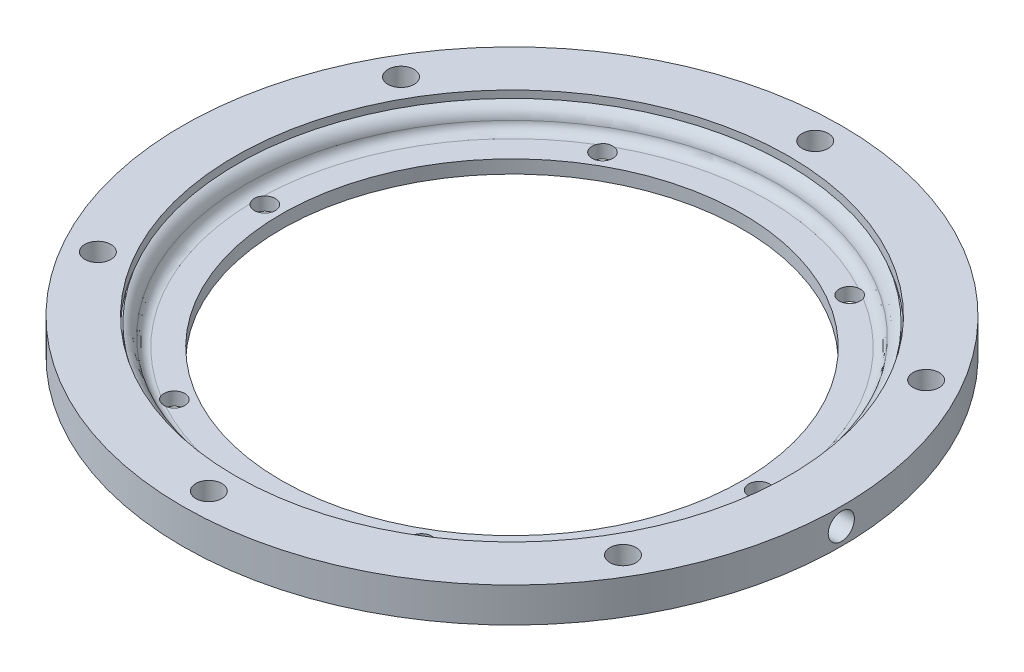
SolidWorks part; units mm, degrees
note: '?' marks a value the reader was unsure of.
ref_plane "Front" through (0, 0, 0) normal (0, 0, 1) x (1, 0, 0)
ref_plane "Top" through (0, 0, 0) normal (0, 1, 0) x (1, 0, 0)
ref_plane "Right" through (0, 0, 0) normal (1, 0, 0) x (0, 0, -1)
ref_axis "Axis1" through (0, 12.8283, 0) along (0, -1, 0)?
sketch "Sketch1" plane through (0, 0, 0) normal (0, 0, 1) x (1, 0, 0)
  line L0 (0, 8.551) -> (0, -4.9357) construction
  line L1 (100, 12.2174) -> (100, 1.6954)
  line L2 (100, 12.2174) -> (84, 12.2174)
  line L3 (84, 12.2174) -> (84, 9.0402)
  line L4 (87, 1.6954) -> (100, 1.6954)
  line L5 (70.016, 0) -> (85.5, 0)
  line L6 (70.016, 0) -> (100, 12.2174) construction
  line L7 (87, 1.6954) -> (87, 3.7334)
  line L9 (70.016, 4) -> (70.016, 0)
  line L10 (84, 9.0402) -> (87, 3.7334) construction
  line L11 (85.5, 0) -> (85.5, 3.048)
  line L12 (83.5, 10.3485) -> (83.5, 8.8172)
  line L13 (77.5, 4) -> (70.016, 4)
  arc A0 (83.5, 8.8172) -> (85.5, 3.048) centre (85.008, 6.1087) ccw
  arc A1 (83.5, 10.3485) -> (80.5444, 6.6797) centre (85.008, 6.1087) ccw
  arc A2 (77.5, 4) -> (80.5444, 6.6797) centre (77.5, 7.0692) ccw
  arc A3 (87, 3.7334) -> (84, 9.0402) centre (85.008, 6.1087) ccw
  point P17 (85.5, 6.3868)
  dimension "D8" = 6.2
  dimension "D9" = 9
  dimension "D2" = 12.2174
  dimension "D3" = 29.984
  dimension "D4" = 16
  dimension "D5" = 10.522
  dimension "D6" = 13
  dimension "D7" = 4
  dimension "D10" = 0.5
  dimension "D11" = 200
  dimension "D12" = 155
  dimension "D13" = 1.6954
  dimension "D14" = 140.032
revolve "Revolve2" add sketch "Sketch1" angle 360 about L0
sketch "Sketch2" plane through (0, 0, 0) normal (0, -1, 0) x (1, 0, 0)
  line L0 (0, 0) -> (167.0886, 0) construction
  line L1 (0, 0) -> (86.0025, -148.9607) construction
  line L2 (70.016, 4.1036) -> (70.016, -4.7686) construction
  line L3 (72.016, 3.5121) -> (72.016, -5.9515) construction
  line L4 (77.5, 0) -> (82.984, 0) construction
  line L5 (72.016, 0) -> (77.5, 0) construction
  line L6 (139.657, -6.35) -> (135.2215, -6.35) construction
  line L7 (73.5238, -114.647) -> (75.5358, -118.1318) construction
  arc A0 (45.1091, -56.138) -> (71.1715, -10.9966) centre (0, 0) ccw
  arc A1 (51.9792, -64.6878) -> (82.0109, -12.6714) centre (0, 0) ccw
  circle A2 centre (0, 0) radius 77.5 construction
  circle A3 centre (0, 0) radius 70.016 construction
  arc A4 (82.0109, -12.6714) -> (71.1715, -10.9966) centre (76.5912, -11.834) ccw
  arc A5 (45.1091, -56.138) -> (51.9792, -64.6878) centre (48.5441, -60.4129) ccw
  dimension "D2" = 155
  dimension "D1" = 60
  dimension "D3" = 2
  dimension "D4" = 6.35
  dimension "D5" = 6.35
extrude "Cut-Extrude1" cut sketch "Sketch2" against normal offset from surface (2.916 mm away) 3.81
pattern_circular "CirPattern1" count 6 over 360 about axis through (0, 0, 0) along (0, 1, 0) of "Cut-Extrude1"
sketch "Sketch3" plane through (0, 1.6954, 0) normal (0, -1, 0) x (1, 0, 0)
  line L0 (0, 0) -> (87, 50.2295) construction
  line L1 (0, 0) -> (154.2972, -89.0835) construction
  line L2 (0, 0) -> (63.0511, 0) construction
  line L3 (88.5604, 41.9649) -> (80.7379, 37.4486)
  line L4 (80.7379, -37.4486) -> (88.5604, -41.9649)
  line L5 (100, 4.9183) -> (100, -33.5059) construction
  line L6 (98, 8.5668) -> (98, -35.0892) construction
  line L7 (89, 7.4564) -> (89, -22.8744) construction
  line L8 (87, -1.1233) -> (87, -18.1031) construction
  arc A0 (88.5604, -41.9649) -> (88.5604, 41.9649) centre (0, 0) ccw
  arc A1 (80.7379, -37.4486) -> (80.7379, 37.4486) centre (0, 0) ccw
  circle A2 centre (0, 0) radius 87 construction
  circle A3 centre (0, 0) radius 100 construction
  dimension "D1" = 60
  dimension "D2" = 30
  dimension "D3" = 7.9375
  dimension "D4" = 7.9375
  dimension "D5" = 2
  dimension "D6" = 2
extrude "Cut-Extrude2" cut sketch "Sketch3" against normal blind 10
pattern_circular "CirPattern2" count 6 over 360 about axis through (0, 0, 0) along (0, 1, 0) of "Cut-Extrude2"
sketch "Sketch5" plane through (0, 4, 0) normal (0, 1, 0) x (-1, 0, 0)
  line L0 (0, 0) -> (-37.5, -64.9519) construction
  line L1 (17.7406, -10.2426) -> (-18.7249, 10.8108) construction
  line L2 (0, 0) -> (0, -87.4239) construction
  circle A0 centre (-37.5, -64.9519) radius 3.175
  dimension "D1" = 6.35
  dimension "D2" = 150
  dimension "D3" = 30
extrude "Cut-Extrude3" cut sketch "Sketch5" against normal through all and the other way through all
pattern_circular "CirPattern3" count 6 over 360 about axis through (0, 0, 0) along (0, 1, 0) of "Cut-Extrude3"
sketch "Sketch8" plane through (0, 0, 0) normal (0, 0, 1) x (1, 0, 0)
  line L1 (89, 11.6954) -> (98, 11.6954)
  line L2 (89, 11.6954) -> (89, 1.6954)
  line L3 (89, 1.6954) -> (98, 1.6954)
  line L4 (98, 11.6954) -> (98, 1.6954)
  line L5 (88.5604, 1.6954) -> (98, 1.6954) construction
  line L6 (88.5604, 11.6954) -> (98, 11.6954) construction
  line L7 (89, 1.6954) -> (89, 11.6954) construction
  line L8 (98, 1.6954) -> (98, 11.6954) construction
  line L9 (0, 29.5183) -> (0, -14.1535) construction
revolve "Revolve3" add sketch "Sketch8" angle 5 mid plane about L9
sketch "Sketch7" plane through (0, 0, 0) normal (0, 0, 1) x (1, 0, 0)
  line L0 (100, 6.9564) -> (169.66, 6.9564) construction
  line L1 (100, 1.6954) -> (100, 12.2174) construction
  line L2 (85.5, 0) -> (85.5, 3.048) construction
  line L3 (100, 6.9564) -> (85.5, 6.9564)
  line L4 (100, 6.9564) -> (100, 10.9251)
  line L5 (100, 10.9251) -> (85.5, 10.9251)
  line L6 (85.5, 6.9564) -> (85.5, 10.9251)
  dimension "D1" = 7.9375
revolve "Cut-Revolve3" cut sketch "Sketch7" angle 360 about L0
sketch "Sketch9" plane through (0, 12.2174, 0) normal (0, 1, 0) x (-1, 0, 0)
  line L0 (0, 0) -> (-153.3926, -88.5612) construction
  line L1 (0, 0) -> (-88.4835, 0) construction
  circle A0 centre (-79.6735, -45.9995) radius 3.9687
  circle A1 centre (0, 0) radius 91.999 construction
  dimension "D2" = 183.998
  dimension "D3" = 7.9375
  dimension "D1" = 30
extrude "Cut-Extrude4" cut sketch "Sketch9" against normal through all
pattern_circular "CirPattern4" count 6 over 360 about axis through (0, 0, 0) along (0, 1, 0) of "Cut-Extrude4"
sketch "Sketch10" plane through (0, 0, 0) normal (0, 0, 1) x (1, 0, 0)
  line L0 (168.7798, 6.9564) -> (150.847, 6.9564) construction
  line L1 (100, 6.9564) -> (169.66, 6.9564) construction
  line L2 (106.35, 9.9564) -> (106.35, 10.9251)
  line L3 (106.35, 10.9251) -> (119.05, 10.9251) construction
  line L4 (119.05, 10.9251) -> (119.05, 6.9564)
  line L5 (119.05, 6.9564) -> (109.35, 6.9564)
  line L6 (106.35, 10.9251) -> (107.0556, 9.7031)
  line L7 (107.0556, 9.7031) -> (107.7611, 10.9251)
  line L8 (107.7611, 10.9251) -> (108.4667, 9.7031)
  line L9 (108.4667, 9.7031) -> (109.1722, 10.9251)
  line L10 (168.4966, 9.7031) -> (178.8498, 9.7031) construction
  line L11 (107.0556, 9.7031) -> (107.0556, 9.7676) construction
  line L12 (100, 10.9251) -> (100, 12.2174) construction
  line L13 (109.1722, 10.9251) -> (109.8778, 9.7031)
  line L14 (109.8778, 9.7031) -> (110.5833, 10.9251)
  line L15 (110.5833, 10.9251) -> (111.2889, 9.7031)
  line L16 (111.2889, 9.7031) -> (111.9944, 10.9251)
  line L17 (111.9944, 10.9251) -> (112.7, 9.7031)
  line L18 (112.7, 9.7031) -> (113.4056, 10.9251)
  line L19 (113.4056, 10.9251) -> (114.1111, 9.7031)
  line L20 (114.1111, 9.7031) -> (114.8167, 10.9251)
  line L21 (114.8167, 10.9251) -> (115.5222, 9.7031)
  line L22 (115.5222, 9.7031) -> (116.2278, 10.9251)
  line L23 (116.2278, 10.9251) -> (116.9333, 9.7031)
  line L24 (116.9333, 9.7031) -> (117.6389, 10.9251)
  line L25 (117.6389, 10.9251) -> (119.05, 10.9251)
  line L26 (106.35, 9.9564) -> (109.35, 6.9564)
  dimension "D1" = 12.7
  dimension "D2" = 60
  dimension "D3" = 1.4111
  dimension "D4" = 7.9375
  dimension "D5" = 6.35
  dimension "D6" = 135
  dimension "D7" = 6
revolve "Revolve4" [suppressed] add sketch "Sketch10" angle 360 about L0
sketch "Sketch11" [suppressed] plane through (181.55, 0, 0) normal (1, 0, 0) x (0, 0, -1)
  line L1 (1.3748, 9.3376) -> (-1.3748, 9.3376)
  line L2 (-1.3748, 9.3376) -> (-2.7496, 6.9564)
  line L3 (-2.7496, 6.9564) -> (-1.3748, 4.5751)
  line L4 (-1.3748, 4.5751) -> (1.3748, 4.5751)
  line L5 (1.3748, 4.5751) -> (2.7496, 6.9564)
  line L6 (2.7496, 6.9564) -> (1.3748, 9.3376)
  circle A0 centre (0, 6.9564) radius 2.3813 construction
  circle A1 centre (0, 6.9564) radius 3.9687 construction
  dimension "D1" = 4.7625
extrude "Cut-Extrude5" [suppressed] cut sketch "Sketch11" against normal blind 5.08
